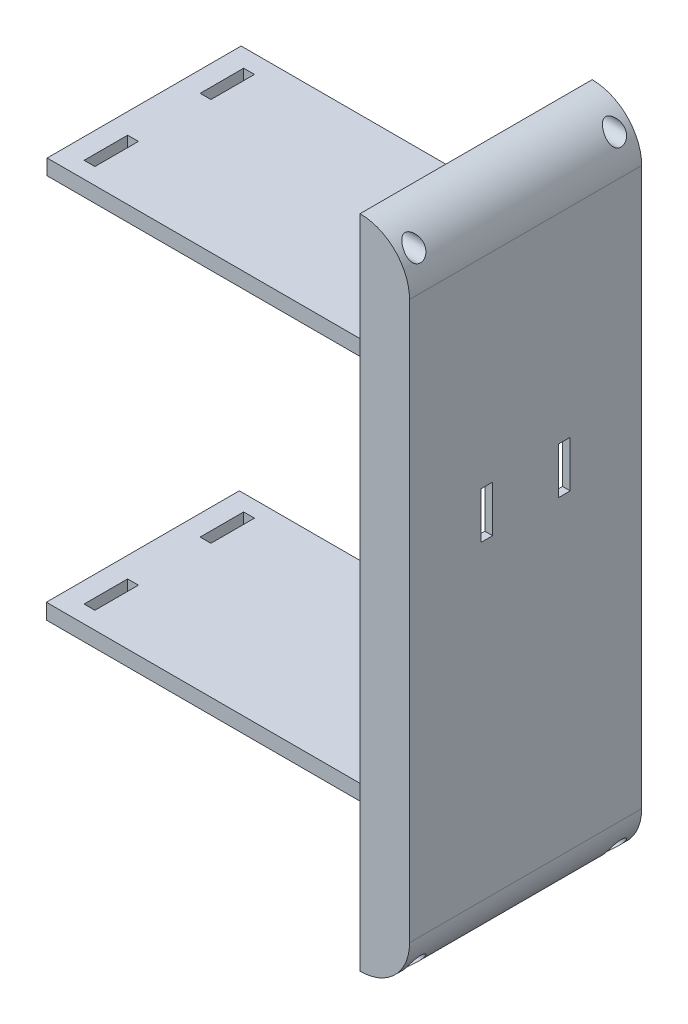
SolidWorks part; units mm, degrees
ref_plane "Front Plane" through (0, 0, 0) normal (0, 0, 1) x (1, 0, 0)
ref_plane "Top Plane" through (0, 0, 0) normal (0, 1, 0) x (1, 0, 0)
ref_plane "Right Plane" through (0, 0, 0) normal (1, 0, 0) x (0, 0, -1)
sketch "Sketch2" plane through (0, 0, 0) normal (0, 0, 1) x (1, 0, 0)
  line L2 (8.128, -45.72) -> (8.128, 45.72)
  line L3 (0, 0) -> (-11.9528, 0) construction
  line L6 (0, 45.72) -> (0, -45.72) construction
  line L11 (0, 53.848) -> (0, -53.848)
  arc A0 (8.128, 45.72) -> (0, 53.848) centre (0, 45.72) ccw
  arc A1 (0, -53.848) -> (8.128, -45.72) centre (0, -45.72) ccw
extrude "Boss-Extrude1" add sketch "Sketch2" along normal mid plane 38.1
sketch "Sketch4" plane through (0, 0, 0) normal (-1, 0, 0) x (0, 0, 1)
  line L0 (0, 29) -> (0, 6) construction
  line L10 (-5.65, 6) -> (5.65, 6) construction
  line L16 (0, 6) -> (0, 2.6928) construction
  line L17 (-15.7447, 30.2928) -> (15.7953, 30.2928)
  line L18 (15.7953, 30.2928) -> (15.7953, -30.2472)
  line L19 (-15.7447, -30.2472) -> (15.7953, -30.2472)
  line L20 (-15.7447, 30.2928) -> (-15.7447, -30.2472)
  line L21 (0, 0) -> (-21.5921, 0) construction
  line L24 (-7.3275, 5.32) -> (-5.4225, 5.32)
  line L25 (-7.3275, 5.32) -> (-7.3275, 12.94)
  line L26 (-7.3275, 12.94) -> (-5.4225, 12.94)
  line L27 (-5.4225, 5.32) -> (-5.4225, 12.94)
  line L30 (5.4225, 12.94) -> (7.3275, 12.94)
  line L31 (5.4225, 12.94) -> (5.4225, 5.32)
  line L32 (5.4225, 5.32) -> (7.3275, 5.32)
  line L33 (7.3275, 12.94) -> (7.3275, 5.32)
  circle A0 centre (-16.4664, -50.7563) radius 1.524
  circle A1 centre (16.4664, -50.7563) radius 1.524
  circle A2 centre (16.4664, 50.7563) radius 1.524
  circle A3 centre (-16.4664, 50.7563) radius 1.524
  point P0 (0, 0)
  point P1 (-6.375, 9.13)
  point P30 (0, 0)
  point P31 (0, 0)
  point P32 (0, 0)
  dimension "D1" = 3.048
  dimension "D2" = 11.3
  dimension "D3" = 7.62
  dimension "D4" = 1.905
extrude "Cut-Extrude4" cut sketch "Sketch4" along direction (-1, 0, 0) on the side of the normal blind 0.508 and the other way blind 6.858 contours L33 L30 L31 L32 | L24 L27 L26 L25 | L17 L20 L19 L18 L27 L24 L25 L26 L30 L33 L32 L31 region at (0, -0.1178, 0.0257) region at (0, 9.13, -6.375) region at (0, 9.13, 6.375)
extrude "Cut-Extrude5" cut sketch "Sketch4<3>" against normal blind 34.798 contours L24 L27 L26 L25 | L33 L30 L31 L32 region at (0, 9.13, -6.375) region at (0, 9.13, 6.375)
sketch "Sketch4<3>" plane through (0, 0, 0) normal (-1, 0, 0) x (0, 0, 1) same geometry as "Sketch4"
sketch "Sketch5" plane through (0, 0, 0) normal (-1, 0, 0) x (0, 0, 1)
  line L1 (-15.7447, -30.2472) -> (15.9345, -30.2472)
  line L2 (-15.7447, -30.2472) -> (-15.7447, -32.7872)
  line L3 (-15.7447, -32.7872) -> (15.9345, -32.7872)
  line L4 (15.9345, -30.2472) -> (15.9345, -32.7872)
  line L6 (15.7953, 30.2928) -> (-16.0459, 30.2928)
  line L7 (15.7953, 30.2928) -> (15.7953, 32.8328)
  line L8 (15.7953, 32.8328) -> (-16.0459, 32.8328)
  line L9 (-16.0459, 30.2928) -> (-16.0459, 32.8328)
  dimension "D1" = 2.54
extrude "Boss-Extrude2" add sketch "Sketch5" along normal blind 54.61
sketch "Sketch6" plane through (0, 32.8328, 0) normal (0, 1, 0) x (1, 0, 0)
  line L0 (0, 0) -> (-4.4934, 0) construction
  line L1 (-49.4781, 13.0976) -> (-51.2493, 13.0976)
  line L2 (-49.4781, 13.0976) -> (-49.4781, 5.9481)
  line L3 (-49.4781, 5.9481) -> (-51.2493, 5.9481)
  line L4 (-51.2493, 13.0976) -> (-51.2493, 5.9481)
  line L5 (-51.2493, -13.0976) -> (-51.2493, -5.9481)
  line L6 (-49.4781, -5.9481) -> (-51.2493, -5.9481)
  line L7 (-49.4781, -13.0976) -> (-49.4781, -5.9481)
  line L8 (-49.4781, -13.0976) -> (-51.2493, -13.0976)
  point P11 (-49.4781, 5.9481)
extrude "Cut-Extrude6" cut sketch "Sketch6" against normal blind 90.782
extrude "Cut-Extrude7" cut sketch "Sketch4<5>" against normal blind 90.782 contours A1 | A2 | A3 | A0 region at (0, -50.7563, 16.4664) region at (0, 50.7563, 16.4664) region at (0, 50.7563, -16.4664)
sketch "Sketch4<5>" plane through (0, 0, 0) normal (-1, 0, 0) x (0, 0, 1) same geometry as "Sketch4"
